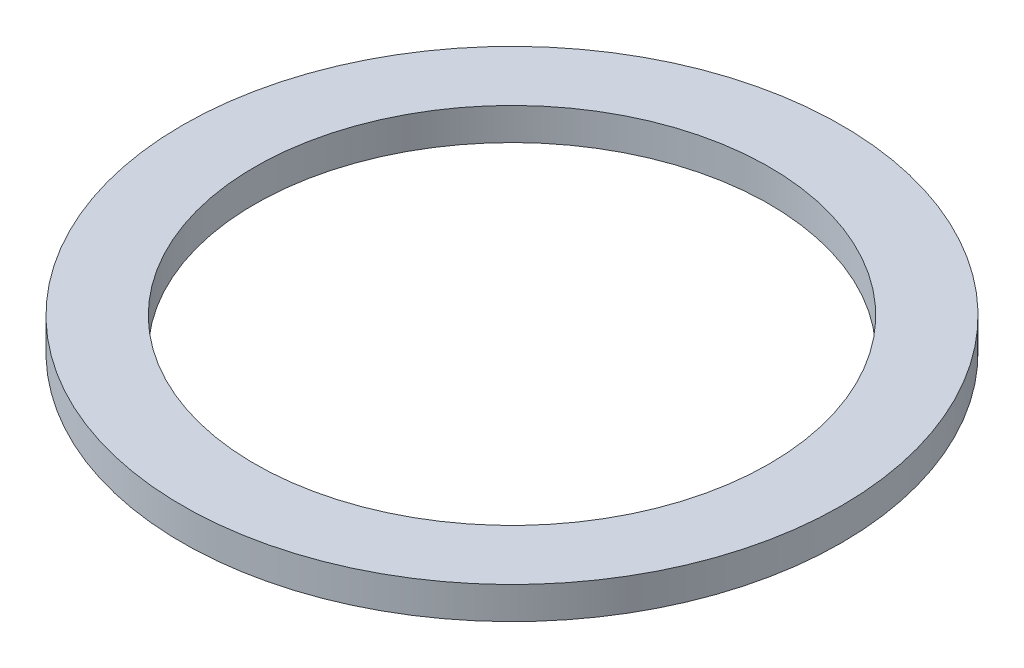
SolidWorks part; units mm, degrees
ref_plane "Front Plane" through (0, 0, 0) normal (0, 0, 1) x (1, 0, 0)
ref_plane "Top Plane" through (0, 0, 0) normal (0, 1, 0) x (1, 0, 0)
ref_plane "Right Plane" through (0, 0, 0) normal (1, 0, 0) x (0, 0, -1)
sketch "Sketch1" plane through (0, 0, 0) normal (0, 0, 1) x (1, 0, 0)
  line L0 (0, -200000) -> (0, 218797.9879) construction
  line L1 (130.175, 154.6921) -> (130.175, 141.9921) construction
  line L4 (101.6, 141.9921) -> (101.6, 154.6921) construction
  line L5 (0, -200000) -> (0, 218797.9879) construction
  line L6 (130.175, 151.6379) -> (130.175, 138.9379)
  line L7 (101.6, 151.6379) -> (130.175, 151.6379)
  line L8 (130.175, 138.9379) -> (101.6, 138.9379)
  line L9 (101.6, 138.9379) -> (101.6, 151.6379)
  point P8 (101.6, 138.9379)
  point P10 (130.175, 138.9379)
  point P12 (130.175, 151.6379)
  point P15 (101.6, 151.6379)
revolve "Revolve1" add sketch "Sketch1" angle 360 about L5
